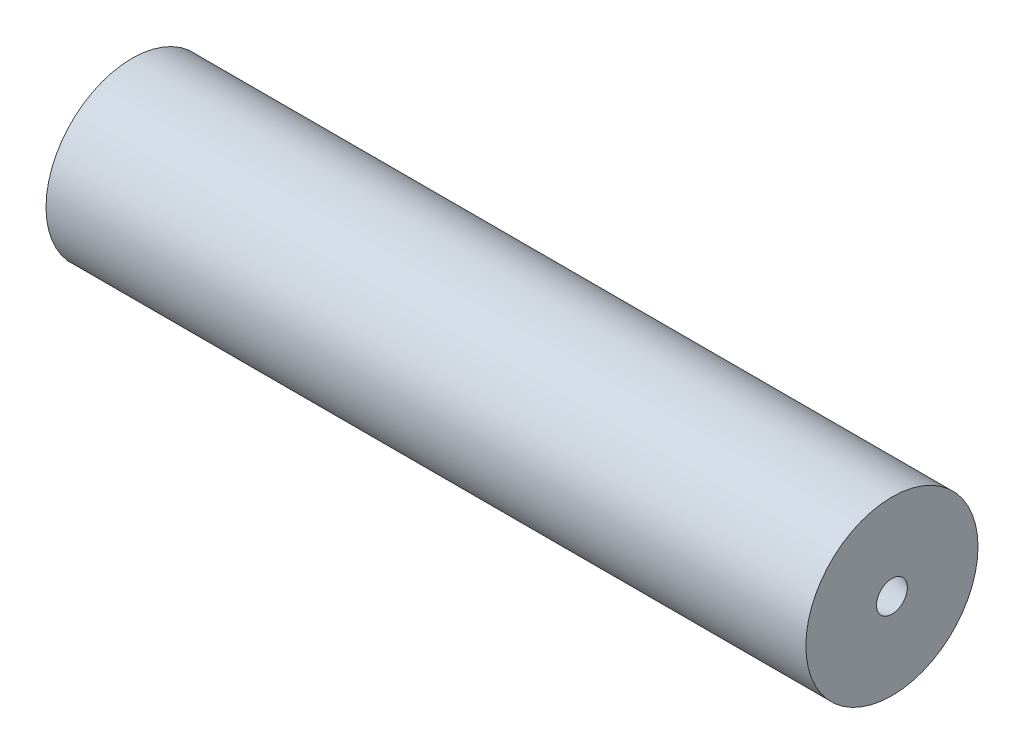
SolidWorks part; units mm, degrees
ref_plane "Front Plane" through (0, 0, 0) normal (0, 0, 1) x (1, 0, 0)
ref_plane "Top Plane" through (0, 0, 0) normal (0, 1, 0) x (1, 0, 0)
ref_plane "Right Plane" through (0, 0, 0) normal (1, 0, 0) x (0, 0, -1)
sketch "Sketch1" plane through (0, 0, 0) normal (0, 0, 1) x (1, 0, 0)
  line L0 (0, 12.7) -> (196.85, 12.7)
  line L1 (196.85, 12.7) -> (196.85, 26.162)
  line L2 (196.85, 26.162) -> (241.3, 26.162)
  line L3 (241.3, 26.162) -> (241.3, 0)
  line L6 (0, 12.7) -> (0, 31)
  line L8 (259.36, 10.7696) -> (259.36, 0)
  line L9 (259.36, 0) -> (241.3, 0)
  line L10 (0, 0) -> (298.2335, 0) construction
  line L11 (259.36, 10.7696) -> (273.6661, 5.5626)
  line L12 (273.6661, 5.5626) -> (273.6661, 31)
  line L14 (273.6661, 31) -> (0, 31)
  point P12 (259.36, 5.3848)
  dimension "D1" = 26.162
  dimension "D2" = 12.7
  dimension "D3" = 62
  dimension "D4" = 44.45
  dimension "D5" = 196.85
  dimension "D6" = 18.06
  dimension "D7" = 10.7696
  dimension "D8" = 5.5626
  dimension "D9" = 14.3061
revolve "Revolve1" add sketch "Sketch1" angle 360 about L10
sketch "Sketch3" plane through (241.3, 0, 0) normal (-1, 0, 0) x (0, 0, 1)
  circle A1 centre (0, 0) radius 6.477 construction
  circle A2 centre (0, 6.477) radius 0.8065
  circle A3 centre (4.5799, 4.5799) radius 0.8065
  circle A4 centre (6.477, 0) radius 0.8065
  circle A5 centre (4.5799, -4.5799) radius 0.8065
  circle A6 centre (0, -6.477) radius 0.8065
  circle A7 centre (-4.5799, -4.5799) radius 0.8065
  circle A8 centre (-6.477, 0) radius 0.8065
  circle A9 centre (-4.5799, 4.5799) radius 0.8065
  point P21 (0, 0)
  dimension "D1" = 12.954
  dimension "D2" = 1.6129
  dimension "D3" = 8
extrude "Cut-Extrude1" cut sketch "Sketch3" against normal up to next
